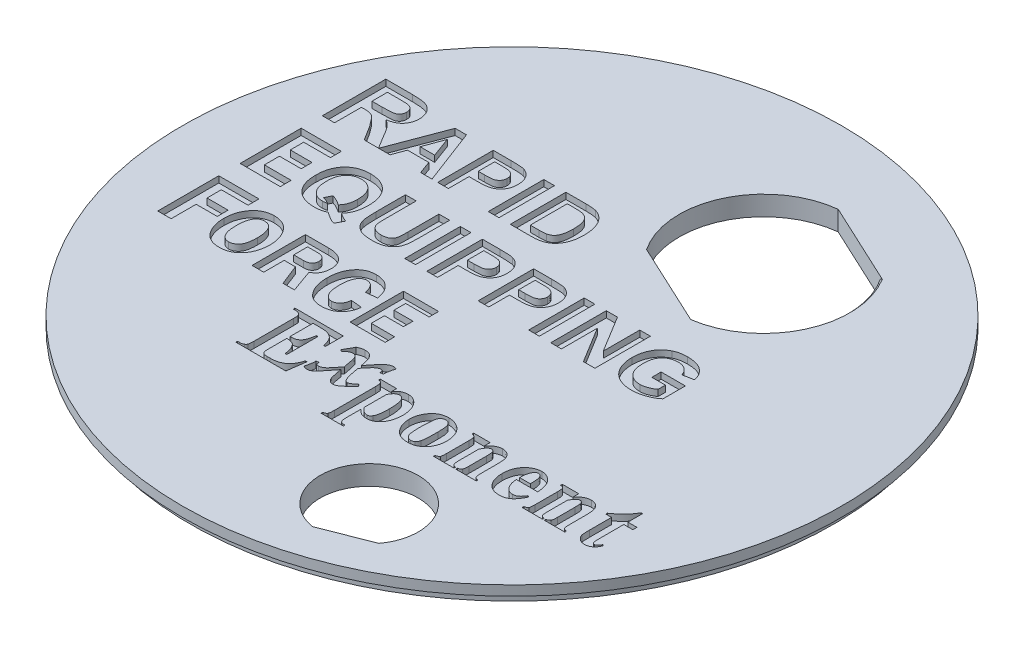
SolidWorks part; units mm, degrees
material "6061 Alloy"
ref_plane "Front Plane" through (0, 0, 0) normal (0, 0, 1) x (1, 0, 0)
ref_plane "Top Plane" through (0, 0, 0) normal (0, 1, 0) x (1, 0, 0)
ref_plane "Right Plane" through (0, 0, 0) normal (1, 0, 0) x (0, 0, -1)
sketch "Sketch1" plane through (0, 0, 0) normal (0, 1, 0) x (1, 0, 0)
  circle A0 centre (0, 0) radius 20.828
  dimension "D1" = 41.656
extrude "Boss-Extrude1" add sketch "Sketch1" along normal blind 1.27
sketch "Sketch2" plane through (0, 1.27, 0) normal (0, 1, 0) x (1, 0, 0)
  circle A0 centre (0, 0) radius 20.32
  circle A1 centre (0, 0) radius 20.828
  circle A2 centre (0, 0) radius 20.828 construction
  dimension "D1" = 0.508
extrude "Cut-Extrude2" cut sketch "Sketch2" against normal blind 0.635
sketch "Sketch3" plane through (0, 1.27, 0) normal (0, 1, 0) x (1, 0, 0)
  line L0 (-8.2448, 26.8258) -> (32.8471, 7.6643) construction
  line L1 (0, 0) -> (8.8023, 18.8766) construction
  line L2 (4.5821, 16.5355) -> (9.7216, 14.1389)
  line L3 (0.6372, 8.0756) -> (5.7766, 5.679)
  arc A0 (5.7766, 5.679) -> (9.7216, 14.1389) centre (5.1794, 11.1073) ccw
  circle A1 centre (0, 0) radius 20.828 construction
  arc A2 (4.5821, 16.5355) -> (0.6372, 8.0756) centre (5.1794, 11.1073) ccw
  circle A3 centre (0, 0) radius 20.32 construction
  point P1 (20.32, 0)
  dimension "D1" = 10.922
  dimension "D3" = 4.6672
  dimension "D4" = 65
  dimension "D2" = 12.2555
extrude "Cut-Extrude3" cut sketch "Sketch3" against normal through all
chamfer "Chamfer1" distance 0.127 angle 45 1 edges at (10.1287, 1.27, -8.7993)
sketch "Sketch13" plane through (0, 0, 0) normal (0, -1, 0) x (1, 0, 0)
  line L0 (8.4392, 17.0695) -> (5.3418, 18.2771)
  line L1 (-5.0512, 24.3244) -> (0.5277, 22.1493) construction
  line L2 (7.5658, 19.4053) -> (0, 0) construction
  arc A0 (5.3418, 18.2771) -> (8.4392, 17.0695) centre (5.9079, 15.153) ccw
  circle A1 centre (0, 0) radius 20.828 construction
  point P10 (5.1794, -11.1073)
  dimension "D3" = 6.35
  dimension "D4" = 2.7051
  dimension "D1" = 16.2639
  dimension "D2" = 133.7
extrude "Cut-Extrude5" cut sketch "Sketch13" against normal through all
sketch "Sketch12" plane through (0, 0, 0) normal (0, -1, 0) x (1, 0, 0)
  line L0 (-10.2147, -4.2027) -> (-10, -4.6631) construction
  line L1 (-19.7462, 0.4611) -> (-7.6606, 6.0967)
  line L2 (-20.514, -1.6486) -> (-14.8784, -13.7342)
  line L3 (-12.7688, -14.502) -> (-0.6831, -8.8664)
  line L4 (-5.5509, 5.3289) -> (0.0847, -6.7568)
  line L5 (-21.185, -0.2098) -> (0.7556, -8.1955) construction
  line L6 (-14.2075, -15.1729) -> (-6.2218, 6.7676) construction
  line L8 (0, 0) -> (-10, -4.6631) construction
  arc A0 (-20.514, -1.6486) -> (-19.7462, 0.4611) centre (-19.0753, -0.9777) cw
  arc A1 (-12.7688, -14.502) -> (-14.8784, -13.7342) centre (-13.4397, -13.0633) cw
  arc A2 (0.0847, -6.7568) -> (-0.6831, -8.8664) centre (-1.3541, -7.4277) cw
  arc A3 (-5.5509, 5.3289) -> (-7.6606, 6.0967) centre (-6.9897, 4.658) ccw
  point P0 (-10.2147, -4.2027)
  point P3 (-10, -4.6631)
  point P22 (5.9079, 15.153)
  point P23 (5.1794, -11.1073)
  dimension "D3" = 16.51
  dimension "D4" = 1.5875
  dimension "D1" = 90
  dimension "D2" = 25.1908
  dimension "D5" = 0.508
  dimension "D6" = 10
extrude "Cut-Extrude4" cut sketch "Sketch12" against normal blind 0.508
sketch "Sketch16" plane through (0, 1.27, 0) normal (0, 1, 0) x (1, 0, 0)
  line L0 (-17.78, 5.08) -> (-17.78, -0.254) construction
  line L1 (-17.78, -0.254) -> (-17.78, -5.588) construction
  text T0 "R" font "Arial" height in points 16
  text T1 "E" font "Franklin Gothic Medium" height in points 16
  text T2 "F" font "Franklin Gothic Medium" height in points 16
  text T3 "APID" font "Arial" height in points 14
  text T4 "QUIPPING" font "Arial" height in points 14
  text T5 "ORCE" font "Franklin Gothic Medium" height in points 14
  text T6 "E  ponent" font "Times New Roman" height in points 16
  text T7 "x" font "Palatino Linotype" height in points 16
  dimension "D1" = 4.064
  dimension "D2" = 5.334
  dimension "D3" = 17.78
  dimension "D4" = 5.08
  dimension "D5" = 3.302
  dimension "D6" = 2.794
  dimension "D7" = 7.62
  dimension "D8" = 10.414
  dimension "D9" = 3.81
  dimension "D10" = 0.889
extrude "Cut-Extrude7" cut sketch "Sketch16" against normal offset from surface (0.4064 mm away) 0.3556 up to face at (-10.2147, 0.508, -4.2027)
sketch "Sketch17" plane through (0, 1.27, 0) normal (0, 1, 0) x (1, 0, 0)
  circle A0 centre (0, 0) radius 21.336
  circle A1 centre (0, 0) radius 20.32
  circle A3 centre (0, 0) radius 20.32 construction
  dimension "D1" = 42.672
extrude "Boss-Extrude3" add sketch "Sketch17" against normal up to surface (0.635 mm away) up to face at (0, 0.635, 20.32)
sketch "Sketch18" plane through (0, 0, 0) normal (0, -1, 0) x (1, 0, 0)
  line L0 (-20.514, -1.6486) -> (-14.8784, -13.7342) construction
  line L1 (-7.6606, 6.0967) -> (-19.7462, 0.4611) construction
  line L2 (-19.8414, -3.091) -> (-19.7099, 0.478)
  arc A0 (-20.7939, 1.1686) -> (-19.7099, 0.478) centre (-20.0319, 1.1686) ccw
  arc A1 (-19.8414, -3.091) -> (-20.5629, -3.3126) centre (-20.1867, -3.252) ccw
  circle A2 centre (0, 0) radius 20.828 construction
  arc A3 (-20.7939, 1.1686) -> (-20.5629, -3.3126) centre (-15.0513, -0.7819) ccw
  point P10 (-19.7099, 0.478)
  point P11 (-19.8414, -3.091)
  point P12 (-20.7926, 1.213)
  point P13 (-20.5629, -3.3126)
  dimension "D1" = 1.524
  dimension "D2" = 0.762
  dimension "D3" = 6.0648
extrude "Cut-Extrude14" cut sketch "Sketch18" against normal up to surface (0.508 mm away) up to face at (-10.2147, 0.508, -4.2027)
